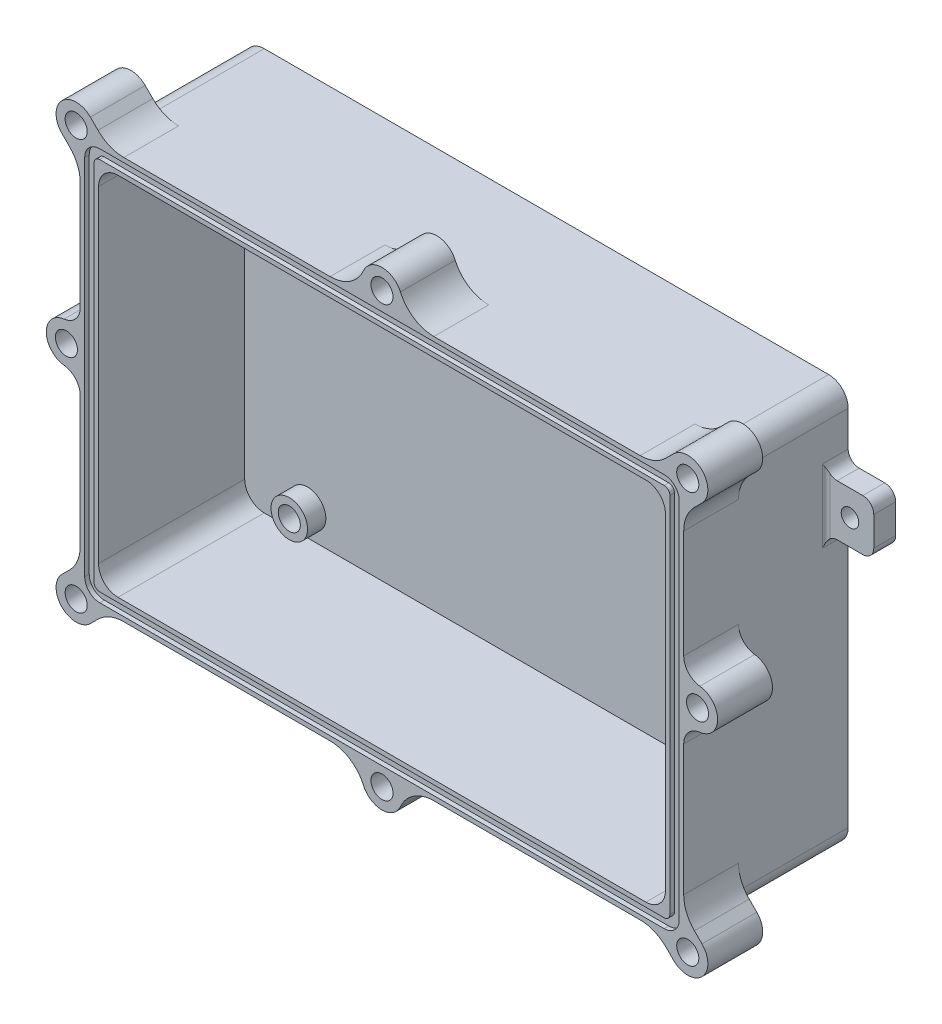
SolidWorks part; units mm, degrees
material "Custom Plastic"
ref_plane "X-Y Datum" through (0, 0, 0) normal (0, 0, 1) x (1, 0, 0)
ref_plane "X-Z Datum" through (0, 0, 0) normal (0, 1, 0) x (1, 0, 0)
ref_plane "Y-Z Datum" through (0, 0, 0) normal (1, 0, 0) x (0, 0, -1)
sketch "Sketch1" plane through (0, 0, 0) normal (0, 0, 1) x (1, 0, 0)
  line L1 (-82.55, 55) -> (82.55, 55)
  line L2 (-82.55, 55) -> (-82.55, -55)
  line L3 (-82.55, -55) -> (82.55, -55)
  line L4 (82.55, 55) -> (82.55, -55)
  line L5 (-82.55, 55) -> (82.55, -55) construction
  line L6 (-82.55, -55) -> (82.55, 55) construction
  point P0 (0, 0)
  dimension "D1" = 165.1
  dimension "D2" = 110
extrude "Boss-Extrude1" add sketch "Sketch1" along normal blind 45
shell "Shell1" thickness 5 removed face at (0, 0, 45)
fillet "Fillet1" radius 5.334 8 edges at (-77.55, -50, 25) (-82.55, -55, 22.5) (82.55, -55, 22.5) (77.55, -50, 25) (82.55, 55, 22.5) (77.55, 50, 25) (-82.55, 55, 22.5) (-77.55, 50, 25)
sketch "Sketch2" plane through (0, 0, 45) normal (0, 0, 1) x (1, 0, 0)
  line L20 (-77.216, -53.7827) -> (77.216, -53.7827)
  line L21 (81.3327, -49.666) -> (81.3327, 49.666)
  line L22 (77.216, 53.7827) -> (-77.216, 53.7827)
  line L23 (-81.3327, 49.666) -> (-81.3327, -49.666)
  line L24 (-77.216, -52.5) -> (77.216, -52.5)
  line L25 (80.05, -49.666) -> (80.05, 49.666)
  line L26 (77.216, 52.5) -> (-77.216, 52.5)
  line L27 (-80.05, 49.666) -> (-80.05, -49.666)
  line L28 (-77.216, -52.5) -> (77.216, -52.5) construction
  line L29 (80.05, -49.666) -> (80.05, 49.666) construction
  line L30 (77.216, 52.5) -> (-77.216, 52.5) construction
  line L31 (-80.05, 49.666) -> (-80.05, -49.666) construction
  line L32 (-78.7673, 49.666) -> (-78.7673, -49.666)
  line L33 (-77.216, -51.2173) -> (77.216, -51.2173)
  line L34 (78.7673, -49.666) -> (78.7673, 49.666)
  line L35 (77.216, 51.2173) -> (-77.216, 51.2173)
  arc A16 (77.216, -53.7827) -> (81.3327, -49.666) centre (77.216, -49.666) ccw
  arc A17 (81.3327, 49.666) -> (77.216, 53.7827) centre (77.216, 49.666) ccw
  arc A18 (-77.216, 53.7827) -> (-81.3327, 49.666) centre (-77.216, 49.666) ccw
  arc A19 (-81.3327, -49.666) -> (-77.216, -53.7827) centre (-77.216, -49.666) ccw
  arc A20 (-80.05, -49.666) -> (-77.216, -52.5) centre (-77.216, -49.666) ccw
  arc A21 (77.216, -52.5) -> (80.05, -49.666) centre (77.216, -49.666) ccw
  arc A22 (80.05, 49.666) -> (77.216, 52.5) centre (77.216, 49.666) ccw
  arc A23 (-77.216, 52.5) -> (-80.05, 49.666) centre (-77.216, 49.666) ccw
  arc A24 (-80.05, -49.666) -> (-77.216, -52.5) centre (-77.216, -49.666) ccw construction
  arc A25 (77.216, -52.5) -> (80.05, -49.666) centre (77.216, -49.666) ccw construction
  arc A26 (80.05, 49.666) -> (77.216, 52.5) centre (77.216, 49.666) ccw construction
  arc A27 (-77.216, 52.5) -> (-80.05, 49.666) centre (-77.216, 49.666) ccw construction
  arc A28 (-77.216, 51.2173) -> (-78.7673, 49.666) centre (-77.216, 49.666) ccw
  arc A29 (-78.7673, -49.666) -> (-77.216, -51.2173) centre (-77.216, -49.666) ccw
  arc A30 (77.216, -51.2173) -> (78.7673, -49.666) centre (77.216, -49.666) ccw
  arc A31 (78.7673, 49.666) -> (77.216, 51.2173) centre (77.216, 49.666) ccw
  dimension "D1" = 2.5
  dimension "D2" = 1.2827
  dimension "D3" = 1.2827
extrude "Cut-Extrude1" cut sketch "Sketch2" against normal blind 1.2446
sketch "Sketch3" plane through (0, 0, 45) normal (0, 0, 1) x (1, 0, 0)
  line L0 (77.216, 49.666) -> (80.9877, 53.4377)
  line L1 (80.9877, 53.4377) -> (83.6625, 56.1125)
  line L2 (79.7734, 60.0016) -> (74.7718, 55)
  line L3 (77.216, 55) -> (-77.216, 55) construction
  line L4 (82.55, -49.666) -> (82.55, 49.666) construction
  line L5 (82.55, -49.666) -> (82.55, 49.666)
  line L6 (77.216, 55) -> (-77.216, 55)
  line L7 (87.5516, 52.2234) -> (82.55, 47.2218)
  arc A0 (82.55, 49.666) -> (77.216, 55) centre (77.216, 49.666) ccw construction
  circle A1 centre (83.6625, 56.1125) radius 3.025
  circle A2 centre (83.6625, 56.1125) radius 5.5
  arc A3 (81.3327, 49.666) -> (77.216, 53.7827) centre (77.216, 49.666) ccw construction
  arc A4 (82.55, 49.666) -> (77.216, 55) centre (77.216, 49.666) ccw
  point P10 (80.1269, 52.5769)
  arc M15 (82.55, 49.666) -> (77.216, 55) centre (77.216, 49.666) ccw
  line M16 (77.216, 55) -> (-77.216, 55)
  dimension "D1" = 6.05
  dimension "D2" = 11
  dimension "D3" = 5
extrude "Boss-Extrude2" add sketch "Sketch3" against normal blind 15 contours A2 L5 L7 M15 | A2 A1 M15 | A2 L2 M16 M15 | A1 region at (82.5376, 58.8282, 45) region at (79.824, 54.4965, 45) region at (77.1925, 56.331, 45) region at (83.881, 49.6425, 45)
sketch "Sketch4" plane through (0, 0, 45) normal (0, 0, 1) x (1, 0, 0)
  line L0 (87.5516, 52.2234) -> (82.55, 47.2218) construction
  line L1 (79.7734, 60.0016) -> (74.7718, 55) construction
  line L2 (77.216, 49.666) -> (80.9877, 53.4377) construction
  line L3 (80.9877, 53.4377) -> (83.6625, 56.1125) construction
  line L4 (82.55, -49.666) -> (82.55, 49.666) construction
  line L5 (77.216, 55) -> (-77.216, 55) construction
  line L6 (87.5516, 52.2234) -> (82.55, 47.2218)
  line L7 (79.7734, 60.0016) -> (74.7718, 55)
  line L8 (77.216, 49.666) -> (80.9877, 53.4377)
  line L9 (80.9877, 53.4377) -> (83.6625, 56.1125)
  line L10 (82.55, -49.666) -> (82.55, 49.666)
  line L11 (77.216, 55) -> (-77.216, 55)
  arc A0 (82.55, 49.666) -> (77.216, 55) centre (77.216, 49.666) ccw construction
  circle A1 centre (83.6625, 56.1125) radius 5.5
  circle A2 centre (83.6625, 56.1125) radius 5.5
  circle A3 centre (83.6625, 56.1125) radius 3.025
  circle A4 centre (83.6625, 56.1125) radius 3.025
  arc A5 (82.55, 49.666) -> (77.216, 55) centre (77.216, 49.666) ccw
  dimension "D1" = 0
  dimension "D2" = 0
extrude "Cut-Extrude2" cut sketch "Sketch4" against normal blind 8 contours A4 region at (82.5376, 58.8282, 45)
mirror "Mirror2" about plane through (0, 0, 0) normal (0, 1, 0) of "Cut-Extrude2", "Boss-Extrude2"
mirror "Mirror3" about plane through (0, 0, 0) normal (1, 0, 0) of "Mirror2"
fillet "Fillet3" radius 10 8 edges at (82.55, 47.2218, 37.5) (74.7718, 55, 37.5) (-74.7718, 55, 37.5) (-82.55, 47.2218, 37.5) (-82.55, -47.2218, 37.5) (-74.7718, -55, 37.5) (74.7718, -55, 37.5) (82.55, -47.2218, 37.5)
sketch "Sketch5" plane through (0, 0, 45) normal (0, 0, 1) x (1, 0, 0)
  line L1 (0, -55) -> (0, -58.7827)
  line L2 (-70.6297, -55) -> (70.6297, -55) construction
  line L3 (-77.216, -53.7827) -> (77.216, -53.7827) construction
  line L4 (-5.5, -58.7827) -> (-5.5, -55)
  line L5 (5.5, -58.7827) -> (5.5, -55)
  line L6 (-70.6297, -55) -> (70.6297, -55)
  circle A0 centre (0, -58.7827) radius 3.025
  circle A1 centre (0, -58.7827) radius 5.5
  line M18 (-70.6297, -55) -> (70.6297, -55)
  dimension "D1" = 6.05
  dimension "D2" = 11
  dimension "D3" = 5
extrude "Boss-Extrude3" add sketch "Sketch5" against normal blind 15 contours A0 | A1 A0 L6 M18 | A1 L5 L6 | A1 L4 M18 region at (2.0785, -56.7042, 45) region at (1.9963, -55.1439, 45) region at (-5.0608, -55.9178, 45) region at (5.0608, -55.9178, 45)
sketch "Sketch6" plane through (0, 0, 45) normal (0, 0, 1) x (1, 0, 0)
  line L0 (-70.6297, -55) -> (70.6297, -55) construction
  line L1 (5.5, -58.7827) -> (5.5, -55) construction
  line L2 (-5.5, -58.7827) -> (-5.5, -55) construction
  line L3 (0, -55) -> (0, -58.7827) construction
  line L4 (-70.6297, -55) -> (70.6297, -55)
  line L5 (5.5, -58.7827) -> (5.5, -55)
  line L6 (-5.5, -58.7827) -> (-5.5, -55)
  line L7 (0, -55) -> (0, -58.7827)
  circle A1 centre (0, -58.7827) radius 5.5
  circle A2 centre (0, -58.7827) radius 5.5
  circle A3 centre (0, -58.7827) radius 3.025
  circle A4 centre (0, -58.7827) radius 3.025
  dimension "D1" = 0
  dimension "D2" = 0
extrude "Cut-Extrude3" cut sketch "Sketch6" against normal blind 8 contours A4 region at (2.0785, -56.7042, 45)
mirror "Mirror10" about plane through (0, 0, 0) normal (0, 1, 0) of "Cut-Extrude3", "Boss-Extrude3"
fillet "Fillet5" radius 10 4 edges at (5.5, 55, 37.5) (-5.5, 55, 37.5) (-5.5, -55, 37.5) (5.5, -55, 37.5)
sketch "Sketch7" plane through (0, 0, 45) normal (0, 0, 1) x (1, 0, 0)
  line L0 (-82.55, 3.0797) -> (-86.3327, 3.0797)
  line L2 (-82.55, 43.0797) -> (-82.55, -43.0797) construction
  line L3 (-81.3327, 49.666) -> (-81.3327, -49.666) construction
  line L4 (-86.3327, 8.5797) -> (-82.55, 8.5797)
  line L5 (-86.3327, -2.4203) -> (-82.55, -2.4203)
  line L6 (-82.55, 43.0797) -> (-82.55, -43.0797)
  circle A0 centre (-86.3327, 3.0797) radius 3.025
  circle A1 centre (-86.3327, 3.0797) radius 5.5
  line M18 (-82.55, 43.0797) -> (-82.55, -43.0797)
  dimension "D1" = 6.05
  dimension "D2" = 11
  dimension "D3" = 5
  dimension "D4" = 40
extrude "Boss-Extrude4" add sketch "Sketch7" against normal blind 15 contours A1 L4 M18 | A1 L5 L6 | L6 A1 A0 M18 | A0 region at (-89.2721, 3.0797, 45) region at (-82.6939, 1.0834, 45) region at (-83.4678, 8.1405, 45) region at (-83.4678, -1.9811, 45)
sketch "Sketch8" plane through (0, 0, 45) normal (0, 0, 1) x (1, 0, 0)
  line L0 (-78.7673, 49.666) -> (-78.7673, -49.666) construction
  line L1 (-82.55, 43.0797) -> (-82.55, -43.0797) construction
  line L2 (-86.3327, -2.4203) -> (-82.55, -2.4203) construction
  line L3 (-86.3327, 8.5797) -> (-82.55, 8.5797) construction
  line L4 (-82.55, 3.0797) -> (-86.3327, 3.0797) construction
  line L5 (-82.55, 43.0797) -> (-82.55, -43.0797)
  line L6 (-86.3327, -2.4203) -> (-82.55, -2.4203)
  line L7 (-86.3327, 8.5797) -> (-82.55, 8.5797)
  line L8 (-82.55, 3.0797) -> (-86.3327, 3.0797)
  circle A1 centre (-86.3327, 3.0797) radius 5.5
  circle A2 centre (-86.3327, 3.0797) radius 5.5
  circle A3 centre (-86.3327, 3.0797) radius 3.025
  circle A4 centre (-86.3327, 3.0797) radius 3.025
  point P0 (-78.7673, 0)
  dimension "D1" = 0
  dimension "D2" = 0
extrude "Cut-Extrude4" cut sketch "Sketch8" against normal blind 8 contours A4 region at (-89.2721, 3.0797, 45)
mirror "Mirror11" about plane through (0, 0, 0) normal (1, 0, 0) of "Cut-Extrude4", "Boss-Extrude4"
fillet "Fillet6" radius 5 4 edges at (82.55, 8.5797, 37.5) (82.55, -2.4203, 37.5) (-82.55, 8.5797, 37.5) (-82.55, -2.4203, 37.5)
sketch "Sketch9" plane through (0, 0, 5) normal (0, 0, 1) x (1, 0, 0)
  circle A0 centre (-60.3534, 42.799) radius 3.025
  circle A1 centre (50.1366, 12.954) radius 3.025
  circle A2 centre (50.1366, -42.926) radius 3.025
  circle A3 centre (-60.3534, -42.926) radius 3.025
  circle A4 centre (-60.3534, -42.926) radius 5
  circle A5 centre (50.1366, -42.926) radius 5
  circle A6 centre (50.1366, 12.954) radius 5
  circle A7 centre (-60.3534, 42.799) radius 5
  point P0 (-60.3534, 42.799)
  point P1 (50.1366, 12.954)
  point P3 (50.1366, -42.926)
  point P5 (-60.3534, -42.926)
  dimension "D1" = 6.05
  dimension "D2" = 10
extrude "Boss-Extrude5" add sketch "Sketch9" along normal blind 5
sketch "Sketch10" plane through (0, 0, 0) normal (0, 0, -1) x (-1, 0, 0)
  line L0 (70.6297, -55) -> (14.1984, -55) construction
  line L1 (50.55, -55) -> (64.55, -55)
  line L2 (50.55, -55) -> (50.55, -68)
  line L3 (50.55, -68) -> (64.55, -68)
  line L4 (64.55, -55) -> (64.55, -68)
  line L15 (-82.55, 13.5089) -> (-82.55, 43.0797) construction
  line L16 (-82.55, 37) -> (-95.55, 37)
  line L17 (-82.55, 37) -> (-82.55, 23)
  line L18 (-82.55, 23) -> (-95.55, 23)
  line L19 (-95.55, 37) -> (-95.55, 23)
  line L20 (-95.55, 23) -> (-82.55, 37) construction
  line L21 (50.55, -68) -> (64.55, -55) construction
  line L22 (-70.6297, 55) -> (-14.1984, 55) construction
  line L23 (82.55, -7.3495) -> (82.55, -43.0797) construction
  circle A0 centre (-89.05, 30) radius 2 construction
  circle A1 centre (57.55, -61.5) radius 2 construction
  dimension "D1" = 4
  dimension "D4" = 4
  dimension "D2" = 14
  dimension "D3" = 13
  dimension "D5" = 25
  dimension "D6" = 25
extrude "Boss-Extrude6" add sketch "Sketch10" against normal blind 6
hole_wizard "M4 Clearance Hole1" positions "Sketch13" profile "Sketch12" hole size "M4" standard "ANSI Metric" end condition through all
sketch "Sketch13" plane through (0, 0, 6) normal (0, 0, 1) x (1, 0, 0)
  point P0 (-57.55, -61.5)
  point P3 (89.05, 30)
sketch "Sketch12" plane through (-57.55, -61.5, 6) normal (1, 0, 0) x (0, -1, 0)
  line L0 (0, 0) -> (0, 6)
  line L1 (0, 6) -> (2.4, 6)
  line L2 (2.4, 6) -> (2.4, 0)
  line L5 (2.4, 0) -> (0, 0)
  line L11 (0, -6.35) -> (0, 107.95) construction
  dimension "Thru Hole Dia." = 4.8
  dimension "Thru Hole Depth" = 6
fillet "Fillet7" radius 3 8 edges at (-50.55, -55, 3) (-64.55, -55, 3) (-64.55, -68, 3) (-50.55, -68, 3) (95.55, 37, 3) (95.55, 23, 3) (82.55, 23, 3) (82.55, 37, 3)
fillet "Fillet8" radius 1 2 edges at (-57.55, -55, 6) (82.55, 30, 6)
